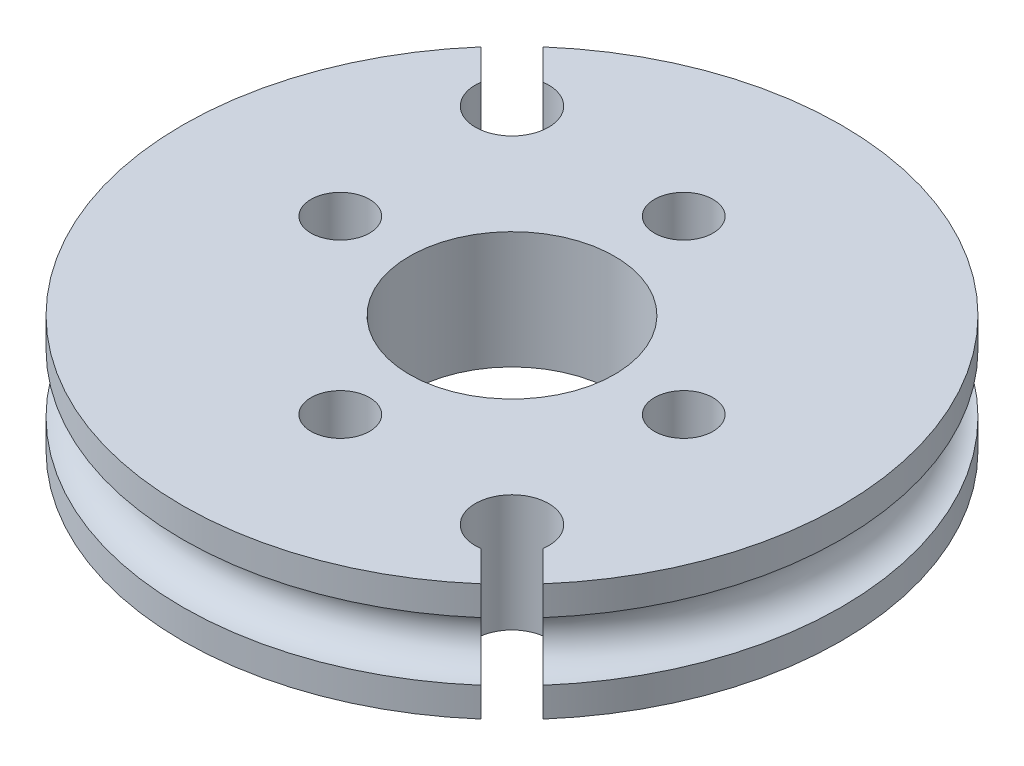
SolidWorks part; units mm, degrees
ref_plane "Front Plane" through (0, 0, 0) normal (0, 0, 1) x (1, 0, 0)
ref_plane "Top Plane" through (0, 0, 0) normal (0, 1, 0) x (1, 0, 0)
ref_plane "Right Plane" through (0, 0, 0) normal (1, 0, 0) x (0, 0, -1)
sketch "Sketch1" plane through (0, 0, 0) normal (0, 1, 0) x (1, 0, 0)
  line L0 (-15.9099, 15.9099) -> (15.9099, -15.9099) construction
  line L1 (0, 0) -> (22.5, 0) construction
  circle A0 centre (0, 0) radius 7
  circle A1 centre (0, 0) radius 22.5
  circle A2 centre (0, 0) radius 11.725 construction
  circle A3 centre (0, 11.725) radius 2
  circle A4 centre (11.725, 0) radius 2
  circle A5 centre (0, -11.725) radius 2
  circle A6 centre (-11.725, 0) radius 2
  circle A7 centre (-12.3744, 12.3744) radius 2.5
  circle A8 centre (0, 0) radius 17.5 construction
  circle A9 centre (12.3744, -12.3744) radius 2.5
  point P21 (12.2301, -12.2301)
  point P22 (-12.4496, 12.4496)
  dimension "D1" = 23.45
  dimension "D2" = 45
  dimension "D3" = 14
  dimension "D4" = 4
  dimension "D6" = 5
  dimension "D7" = 5
  dimension "D5" = 45
extrude "Boss-Extrude1" add sketch "Sketch1" along normal blind 4 and the other way blind 4
sketch "Sketch2" plane through (0, 0, 0) normal (0, 0, 1) x (1, 0, 0)
  line L0 (0, 0) -> (22.5, 0) construction
  line L1 (22.5, -4) -> (22.5, 4) construction
  line L2 (0, 0) -> (0, 4) construction
  line L3 (22.5, 4) -> (-22.5, 4) construction
  circle A0 centre (22.5, 0) radius 2
  dimension "D1" = 4
revolve "Cut-Revolve7" cut sketch "Sketch2" angle 360 about L2
sketch "Sketch3" plane through (0, 0, 0) normal (0, 1, 0) x (1, 0, 0)
  line L0 (-15.9099, 15.9099) -> (15.9099, -15.9099) construction
  line L1 (-18.3848, 16.2635) -> (-13.435, 11.3137)
  line L2 (0, 0) -> (22.5, 0) construction
  line L3 (-13.435, 11.3137) -> (-11.3137, 13.435)
  line L4 (-11.3137, 13.435) -> (-16.2635, 18.3848)
  line L5 (-16.2635, 18.3848) -> (-18.3848, 16.2635)
  line L6 (-15.9099, 15.9099) -> (-17.3241, 17.3241) construction
  line L7 (13.435, -11.3137) -> (11.3137, -13.435)
  line L8 (11.3137, -13.435) -> (16.2635, -18.3848)
  line L9 (16.2635, -18.3848) -> (18.3848, -16.2635)
  line L10 (18.3848, -16.2635) -> (13.435, -11.3137)
  line L11 (17.3241, -17.3241) -> (15.9099, -15.9099) construction
  circle A0 centre (0, 0) radius 22.5 construction
  dimension "D1" = 45
  dimension "D2" = 3
  dimension "D3" = 2
  dimension "D4" = 7
extrude "Cut-Extrude1" cut sketch "Sketch3" against normal blind 4 and the other way blind 4
